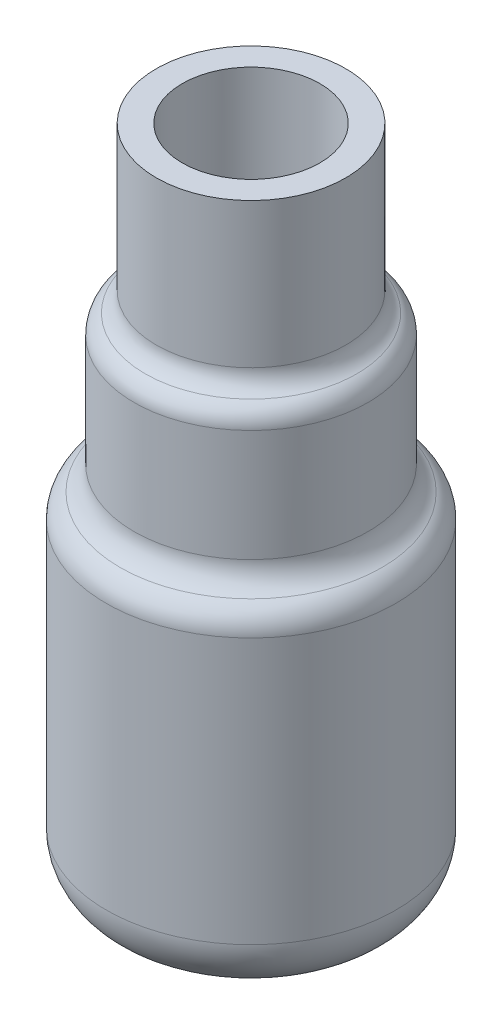
SolidWorks part; units mm, degrees
ref_plane "Спереди" through (0, 0, 0) normal (0, 0, 1) x (1, 0, 0)
ref_plane "Сверху" through (0, 0, 0) normal (0, 1, 0) x (1, 0, 0)
ref_plane "Справа" through (0, 0, 0) normal (1, 0, 0) x (0, 0, -1)
sketch "Эскиз1" plane through (0, 0, 0) normal (0, 1, 0) x (1, 0, 0)
  circle A0 centre (0, 0) radius 21
  circle A1 centre (0, 0) radius 26
  dimension "D1" = 42
  dimension "D2" = 52
extrude "Вытянуть1" add sketch "Эскиз1" along normal blind 60
fillet "Скругление1" radius 10 1 edges at (0, 0, 26)
sketch "Эскиз2" plane through (0, 60, 0) normal (0, 1, 0) x (1, 0, 0)
  circle A0 centre (0, 0) radius 21
  circle A1 centre (0, 0) radius 12.35
  dimension "D1" = 24.7
  dimension "D2" = 42
extrude "Вытянуть2" add sketch "Эскиз2" along normal blind 30 from offset 2
sketch "Эскиз3" plane through (0, 88, 0) normal (0, 1, 0) x (1, 0, 0)
  circle A0 centre (0, 0) radius 12.35
  circle A1 centre (0, 0) radius 17
  dimension "D1" = 24.7
extrude "Вытянуть3" add sketch "Эскиз3" along normal blind 30
fillet "Скругление3" radius 4 1 edges at (0, 88, 17)
fillet "Скругление4" radius 4 1 edges at (0, 88, 21)
fillet "Скругление6" radius 5 1 edges at (0, 60, 21)
fillet "Скругление7" radius 5 1 edges at (0, 60, 26)
fillet "Скругление8" radius 5 1 edges at (0, 58, 21)
fillet "Скругление9" radius 5 1 edges at (0, 58, 12.35)
